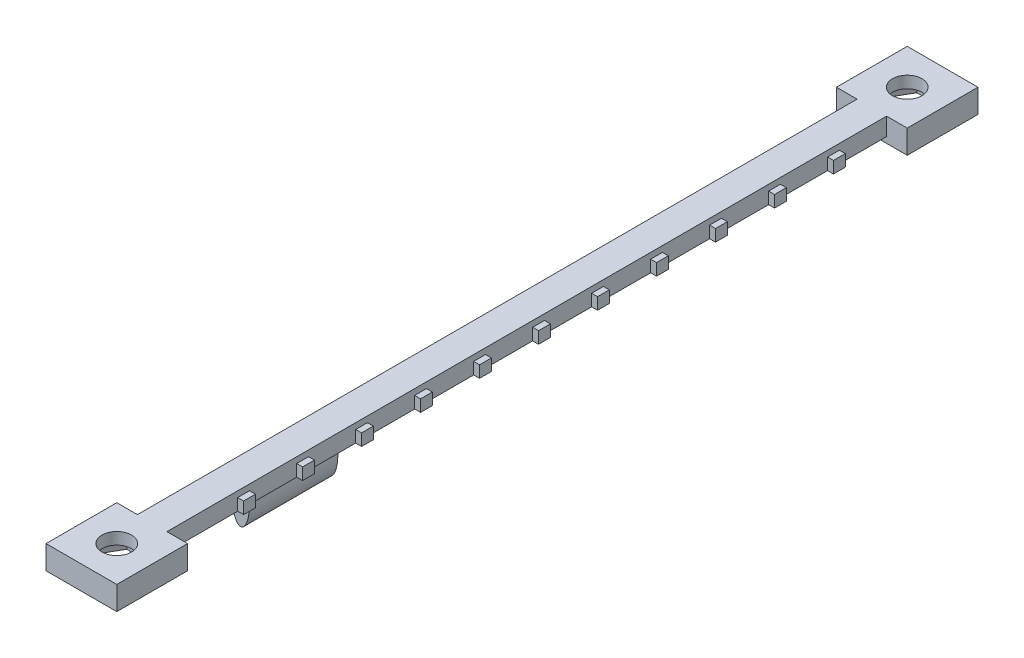
SolidWorks part; units mm, degrees
ref_plane "Front Plane" through (0, 0, 0) normal (0, 0, 1) x (1, 0, 0)
ref_plane "Top Plane" through (0, 0, 0) normal (0, 1, 0) x (1, 0, 0)
ref_plane "Right Plane" through (0, 0, 0) normal (1, 0, 0) x (0, 0, -1)
sketch "Sketch1" plane through (0, 0, 0) normal (0, 1, 0) x (1, 0, 0)
  line L0 (7.2267, 6.096) -> (7.2267, 18.096)
  line L1 (12.2267, 6.096) -> (12.2267, 18.096)
  line L2 (7.2267, 128.096) -> (3.7267, 128.096)
  line L3 (12.2267, 128.096) -> (15.7267, 128.096)
  line L4 (3.7267, 128.096) -> (3.7267, 140.096)
  line L5 (15.7267, 128.096) -> (15.7267, 140.096)
  line L6 (3.7267, 140.096) -> (15.7267, 140.096)
  line L7 (7.2267, 6.096) -> (3.7267, 6.096)
  line L8 (12.2267, 6.096) -> (15.7267, 6.096)
  line L9 (3.7267, 6.096) -> (3.7267, -5.904)
  line L10 (15.7267, 6.096) -> (15.7267, -5.904)
  line L11 (3.7267, -5.904) -> (15.7267, -5.904)
  line L12 (7.2267, 120.096) -> (7.2267, 128.096)
  line L13 (7.2267, 6.096) -> (7.2267, 128.096) construction
  line L14 (-994.5233, 128.096) -> (49005.4767, 128.096) construction
  line L15 (6.2267, 120.096) -> (7.2267, 120.096)
  line L18 (6.2267, 118.096) -> (7.2267, 118.096)
  line L19 (6.2267, 110.096) -> (7.2267, 110.096)
  line L20 (6.2267, 108.096) -> (7.2267, 108.096)
  line L21 (6.2267, 100.096) -> (7.2267, 100.096)
  line L22 (6.2267, 98.096) -> (7.2267, 98.096)
  line L23 (6.2267, 90.096) -> (7.2267, 90.096)
  line L24 (6.2267, 88.096) -> (7.2267, 88.096)
  line L25 (6.2267, 80.096) -> (7.2267, 80.096)
  line L26 (6.2267, 78.096) -> (7.2267, 78.096)
  line L27 (6.2267, 70.096) -> (7.2267, 70.096)
  line L28 (6.2267, 68.096) -> (7.2267, 68.096)
  line L29 (6.2267, 60.096) -> (7.2267, 60.096)
  line L30 (6.2267, 58.096) -> (7.2267, 58.096)
  line L31 (6.2267, 50.096) -> (7.2267, 50.096)
  line L32 (6.2267, 48.096) -> (7.2267, 48.096)
  line L33 (6.2267, 40.096) -> (7.2267, 40.096)
  line L34 (6.2267, 38.096) -> (7.2267, 38.096)
  line L35 (6.2267, 30.096) -> (7.2267, 30.096)
  line L36 (6.2267, 28.096) -> (7.2267, 28.096)
  line L37 (6.2267, 20.096) -> (7.2267, 20.096)
  line L38 (6.2267, 18.096) -> (7.2267, 18.096)
  line L39 (-994.5233, 118.096) -> (49005.4767, 118.096) construction
  line L40 (-994.5233, 120.096) -> (49005.4767, 120.096) construction
  line L41 (12.2267, 120.096) -> (12.2267, 128.096)
  line L42 (12.2267, 6.096) -> (12.2267, 128.096) construction
  line L43 (6.2267, 118.096) -> (6.2267, 120.096)
  line L44 (12.2267, 118.096) -> (13.2267, 118.096)
  line L45 (12.2267, 120.096) -> (13.2267, 120.096)
  line L46 (7.2267, 110.096) -> (7.2267, 118.096)
  line L47 (12.2267, 110.096) -> (12.2267, 118.096)
  line L48 (13.2267, 118.096) -> (13.2267, 120.096)
  line L49 (-994.5233, 110.096) -> (49005.4767, 110.096) construction
  line L50 (-994.5233, 108.096) -> (49005.4767, 108.096) construction
  line L51 (13.2267, 108.096) -> (13.2267, 110.096)
  line L52 (-994.5233, 100.096) -> (49005.4767, 100.096) construction
  line L53 (12.2267, 110.096) -> (13.2267, 110.096)
  line L54 (12.2267, 108.096) -> (13.2267, 108.096)
  line L55 (12.2267, 100.096) -> (13.2267, 100.096)
  line L56 (12.2267, 98.096) -> (13.2267, 98.096)
  line L57 (-994.5233, 98.096) -> (49005.4767, 98.096) construction
  line L58 (12.2267, 90.096) -> (13.2267, 90.096)
  line L59 (-994.5233, 90.096) -> (49005.4767, 90.096) construction
  line L60 (12.2267, 88.096) -> (13.2267, 88.096)
  line L61 (-994.5233, 88.096) -> (49005.4767, 88.096) construction
  line L62 (12.2267, 80.096) -> (13.2267, 80.096)
  line L63 (-994.5233, 80.096) -> (49005.4767, 80.096) construction
  line L64 (12.2267, 78.096) -> (13.2267, 78.096)
  line L65 (-994.5233, 78.096) -> (49005.4767, 78.096) construction
  line L66 (12.2267, 70.096) -> (13.2267, 70.096)
  line L67 (-994.5233, 70.096) -> (49005.4767, 70.096) construction
  line L68 (12.2267, 68.096) -> (13.2267, 68.096)
  line L69 (-994.5233, 68.096) -> (49005.4767, 68.096) construction
  line L70 (12.2267, 60.096) -> (13.2267, 60.096)
  line L71 (-994.5233, 60.096) -> (49005.4767, 60.096) construction
  line L72 (12.2267, 58.096) -> (13.2267, 58.096)
  line L73 (-994.5233, 58.096) -> (49005.4767, 58.096) construction
  line L74 (12.2267, 50.096) -> (13.2267, 50.096)
  line L75 (-994.5233, 50.096) -> (49005.4767, 50.096) construction
  line L76 (12.2267, 48.096) -> (13.2267, 48.096)
  line L77 (-994.5233, 48.096) -> (49005.4767, 48.096) construction
  line L78 (12.2267, 40.096) -> (13.2267, 40.096)
  line L79 (-994.5233, 40.096) -> (49005.4767, 40.096) construction
  line L80 (12.2267, 38.096) -> (13.2267, 38.096)
  line L81 (-994.5233, 38.096) -> (49005.4767, 38.096) construction
  line L82 (12.2267, 30.096) -> (13.2267, 30.096)
  line L83 (-994.5233, 30.096) -> (49005.4767, 30.096) construction
  line L84 (12.2267, 28.096) -> (13.2267, 28.096)
  line L85 (-994.5233, 28.096) -> (49005.4767, 28.096) construction
  line L86 (12.2267, 20.096) -> (13.2267, 20.096)
  line L87 (-994.5233, 20.096) -> (49005.4767, 20.096) construction
  line L88 (12.2267, 18.096) -> (13.2267, 18.096)
  line L89 (-994.5233, 18.096) -> (49005.4767, 18.096) construction
  line L90 (13.2267, 18.096) -> (13.2267, 20.096)
  line L91 (6.2267, 108.096) -> (6.2267, 110.096)
  line L92 (12.2267, 100.096) -> (12.2267, 108.096)
  line L93 (7.2267, 100.096) -> (7.2267, 108.096)
  line L94 (7.2267, 90.096) -> (7.2267, 98.096)
  line L95 (12.2267, 90.096) -> (12.2267, 98.096)
  line L96 (13.2267, 98.096) -> (13.2267, 100.096)
  line L97 (6.2267, 98.096) -> (6.2267, 100.096)
  line L98 (12.2267, 80.096) -> (12.2267, 88.096)
  line L99 (7.2267, 80.096) -> (7.2267, 88.096)
  line L100 (7.2267, 70.096) -> (7.2267, 78.096)
  line L101 (12.2267, 70.096) -> (12.2267, 78.096)
  line L102 (12.2267, 60.096) -> (12.2267, 68.096)
  line L103 (7.2267, 60.096) -> (7.2267, 68.096)
  line L104 (13.2267, 88.096) -> (13.2267, 90.096)
  line L105 (13.2267, 78.096) -> (13.2267, 80.096)
  line L106 (13.2267, 68.096) -> (13.2267, 70.096)
  line L107 (13.2267, 58.096) -> (13.2267, 60.096)
  line L108 (6.2267, 58.096) -> (6.2267, 60.096)
  line L109 (6.2267, 68.096) -> (6.2267, 70.096)
  line L110 (6.2267, 78.096) -> (6.2267, 80.096)
  line L111 (6.2267, 88.096) -> (6.2267, 90.096)
  line L112 (12.2267, 50.096) -> (12.2267, 58.096)
  line L113 (7.2267, 50.096) -> (7.2267, 58.096)
  line L114 (7.2267, 40.096) -> (7.2267, 48.096)
  line L115 (12.2267, 40.096) -> (12.2267, 48.096)
  line L116 (7.2267, 30.096) -> (7.2267, 38.096)
  line L117 (12.2267, 30.096) -> (12.2267, 38.096)
  line L118 (7.2267, 20.096) -> (7.2267, 28.096)
  line L119 (12.2267, 20.096) -> (12.2267, 28.096)
  line L120 (6.2267, 18.096) -> (6.2267, 20.096)
  line L121 (6.2267, 28.096) -> (6.2267, 30.096)
  line L122 (6.2267, 38.096) -> (6.2267, 40.096)
  line L123 (6.2267, 48.096) -> (6.2267, 50.096)
  line L124 (13.2267, 48.096) -> (13.2267, 50.096)
  line L125 (13.2267, 28.096) -> (13.2267, 30.096)
  line L126 (13.2267, 38.096) -> (13.2267, 40.096)
  point P20 (5.4767, 128.096)
  dimension "D1" = 5
  dimension "D4" = 8
  dimension "D5" = 2
  dimension "D6" = 10
  dimension "D7" = 20
  dimension "D8" = 40
  dimension "D9" = 40
extrude "Boss-Extrude1" add sketch "Sketch1" along normal blind 2
sketch "Sketch2" plane through (0, 2, 0) normal (0, 1, 0) x (1, 0, 0)
  line L0 (3.7267, 140.096) -> (15.7267, 140.096)
  line L1 (15.7267, 140.096) -> (15.7267, 128.096)
  line L2 (15.7267, 128.096) -> (12.2267, 128.096)
  line L3 (12.2267, 128.096) -> (15.7267, 128.096) construction
  line L4 (12.2267, 128.096) -> (12.2267, 6.096)
  line L5 (12.2267, 6.096) -> (15.7267, 6.096)
  line L6 (15.7267, 6.096) -> (15.7267, -5.904)
  line L7 (3.7267, -5.904) -> (15.7267, -5.904) construction
  line L8 (15.7267, -5.904) -> (15.7267, 6.096) construction
  line L9 (15.7267, -5.904) -> (3.7267, -5.904)
  line L10 (3.7267, 6.096) -> (3.7267, -5.904) construction
  line L11 (3.7267, -5.904) -> (3.7267, 6.096)
  line L12 (3.7267, 6.096) -> (7.2267, 6.096)
  line L13 (7.2267, 6.096) -> (7.2267, 128.096)
  line L14 (7.2267, 128.096) -> (3.7267, 128.096)
  line L15 (3.7267, 128.096) -> (7.2267, 128.096) construction
  line L16 (3.7267, 140.096) -> (3.7267, 128.096) construction
  line L17 (3.7267, 128.096) -> (3.7267, 140.096)
extrude "Boss-Extrude2" add sketch "Sketch2" along normal blind 1
sketch "Sketch3" plane through (0, 0, 0) normal (0, -1, 0) x (-1, 0, 0)
  line L0 (-15.7267, 128.096) -> (-3.7267, 128.096)
  line L1 (-12.2267, 128.096) -> (-15.7267, 128.096) construction
  line L2 (-15.7267, 128.096) -> (-15.7267, 140.096) construction
  line L3 (-3.7267, 128.096) -> (-3.7267, 140.096)
  line L4 (-3.7267, 140.096) -> (-3.7267, 128.096) construction
  line L5 (-15.7267, 140.096) -> (-3.7267, 140.096) construction
  line L6 (-3.7267, 140.096) -> (-15.7267, 140.096)
  line L7 (-15.7267, 140.096) -> (-15.7267, 128.096)
  line L8 (-3.7267, -5.904) -> (-3.7267, 6.096)
  line L9 (-3.7267, 6.096) -> (-15.7267, 6.096)
  line L10 (-15.7267, 6.096) -> (-15.7267, -5.904)
  line L11 (-15.7267, -5.904) -> (-3.7267, -5.904)
extrude "Boss-Extrude3" add sketch "Sketch3" along normal blind 1 contours L11 L8 L9 L10 | L7 L0 L3 L6
sketch "Sketch4" plane through (0, -1, 0) normal (0, -1, 0) x (-1, 0, 0)
  line L0 (-1015.7267, 134.096) -> (48984.2733, 134.096) construction
  line L1 (-15.7267, 140.096) -> (-15.7267, 128.096) construction
  line L2 (-9.7267, -859.904) -> (-9.7267, 49140.096) construction
  line L3 (-3.7267, 140.096) -> (-15.7267, 140.096) construction
  line L4 (-1015.7267, 0.096) -> (48984.2733, 0.096) construction
  line L11 (-7.3651, 138.096) -> (-11.9839, 138.096)
  line L12 (-11.9839, 138.096) -> (-14.2933, 134.096)
  line L13 (-14.2933, 134.096) -> (-11.9839, 130.096)
  line L14 (-11.9839, 130.096) -> (-7.3651, 130.096)
  line L15 (-7.3651, 130.096) -> (-5.0557, 134.096)
  line L16 (-5.0557, 134.096) -> (-7.3651, 138.096)
  line L17 (-15.7267, 6.096) -> (-15.7267, -5.904) construction
  line L19 (-7.4173, 4.096) -> (-12.0361, 4.096)
  line L20 (-12.0361, 4.096) -> (-14.3455, 0.096)
  line L21 (-14.3455, 0.096) -> (-12.0361, -3.904)
  line L22 (-12.0361, -3.904) -> (-7.4173, -3.904)
  line L23 (-7.4173, -3.904) -> (-5.1079, 0.096)
  line L24 (-5.1079, 0.096) -> (-7.4173, 4.096)
  circle A1 centre (-9.6745, 134.096) radius 4 construction
  circle A2 centre (-9.7267, 0.096) radius 4 construction
  point P5 (-15.7267, 134.096)
  point P10 (-9.7267, 140.096)
  point P31 (-15.7267, 0.096)
extrude "Cut-Extrude1" cut sketch "Sketch4" against normal blind 2 contours L11 L12 L13 L14 L15 L16 | L19 L20 L21 L22 L23 L24
sketch "Sketch5" plane through (0, 1, 0) normal (0, -1, 0) x (-1, 0, 0)
  line L0 (-1005.0557, 134.096) -> (48994.9443, 134.096) construction
  line L1 (-1005.1079, 0.096) -> (48994.8921, 0.096) construction
  line L2 (-9.7267, -995.904) -> (-9.7267, 49004.096) construction
  line L3 (-7.4173, 4.096) -> (-12.0361, 4.096) construction
  circle A0 centre (-9.7267, 0.096) radius 2.5
  circle A1 centre (-9.7267, 134.096) radius 2.5
  point P11 (-9.7267, 4.096)
extrude "Cut-Extrude2" cut sketch "Sketch5" against normal blind 5 contours A1 | A0
sketch "Sketch6" plane through (0, 0, 0) normal (0, -1, 0) x (-1, 0, 0)
  line L0 (-1006.1015, 6.096) -> (48993.8985, 6.096) construction
  line L2 (-1004.9212, 128.096) -> (48995.0788, 128.096) construction
  line L4 (-11.2267, 21.096) -> (-8.2267, 21.096)
  line L5 (-11.2267, 36.096) -> (-8.2267, 36.096)
  line L11 (-12.2267, 21.096) -> (-12.2267, 36.096) construction
  line L14 (-11.2267, 21.096) -> (-11.2267, 36.096)
  line L16 (-8.2267, 21.096) -> (-8.2267, 36.096)
  line L18 (-7.2267, 21.096) -> (-7.2267, 36.096) construction
  line L20 (-1006.1015, 21.096) -> (48993.8985, 21.096) construction
  line L21 (-1006.1015, 36.096) -> (48993.8985, 36.096) construction
  dimension "D1" = 15
  dimension "D2" = 15
extrude "Boss-Extrude4" add sketch "Sketch6" along normal blind 5 contours L4 L16 L5 L14
sketch "Sketch7" plane through (0, 0, -36.096) normal (0, 0, -1) x (-1, 0, 0)
  line L0 (-8.2267, -5) -> (-11.2267, -5)
  line L1 (-11.2267, -5) -> (-11.2267, -1)
  line L2 (-3.7267, -1) -> (-15.7267, -1) construction
  line L3 (-11.2267, -5) -> (-11.2267, 0) construction
  line L4 (-11.2267, -1) -> (-8.2267, -1)
  line L5 (-8.2267, -5) -> (-8.2267, 0) construction
  line L6 (-8.2267, -1) -> (-8.2267, -5)
  ellipse E0 centre (-9.7267, -1) end of major axis (-9.7267, -5) minor radius 1.5 (-11.2267, -1) -> (-8.2267, -1) ccw
  line M2 (-11.2267, 0) -> (-11.2267, -5)
  line M3 (-11.2267, -5) -> (-8.2267, -5)
  line M4 (-8.2267, -5) -> (-8.2267, 0)
extrude "Cut-Extrude3" cut sketch "Sketch7" against normal blind 30 contours E0 L0 M4 | E0 M2 M3 region at (8.5618, -4.1065, -36.096) region at (10.8917, -4.1065, -36.096)
